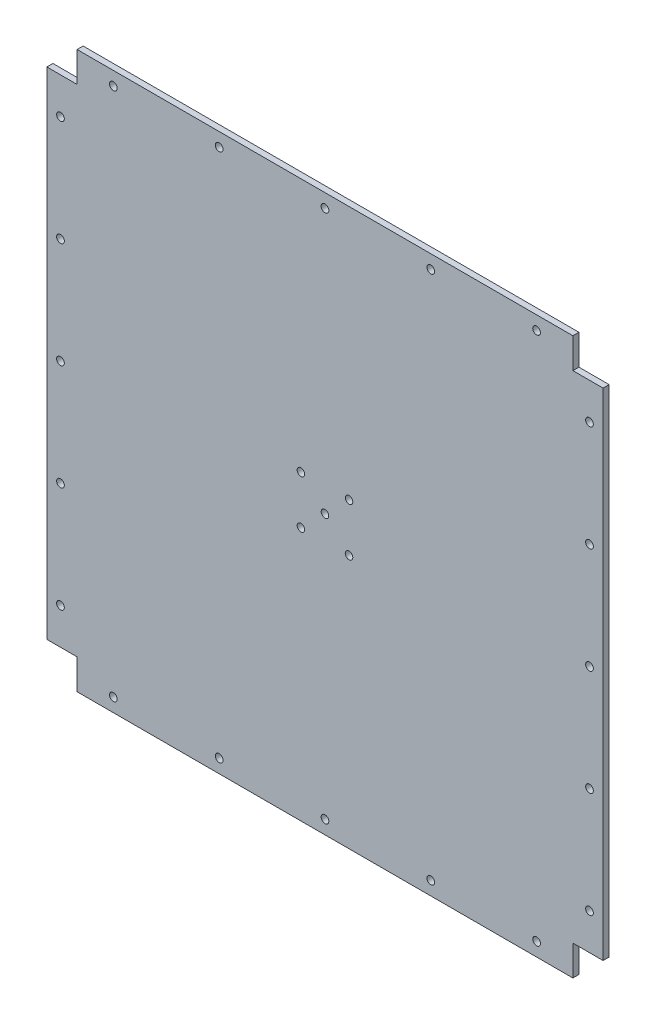
SolidWorks part; units mm, degrees
ref_plane "前视基准面" through (0, 0, 0) normal (0, 0, 1) x (1, 0, 0)
ref_plane "上视基准面" through (0, 0, 0) normal (0, 1, 0) x (1, 0, 0)
ref_plane "右视基准面" through (0, 0, 0) normal (1, 0, 0) x (0, 0, -1)
sketch "草图1" plane through (0, 0, 0) normal (0, 0, 1) x (1, 0, 0)
  line L1 (184, -184) -> (-184, -184)
  line L2 (184, -184) -> (184, 184)
  line L3 (184, 184) -> (-184, 184)
  line L4 (-184, -184) -> (-184, 184)
  line L5 (184, -184) -> (-184, 184) construction
  line L6 (184, 184) -> (-184, -184) construction
  point P0 (0, 0)
  dimension "D1" = 368
  dimension "D2" = 368
extrude "凸台-拉伸1" add sketch "草图1" along normal blind 4
sketch "草图3" plane through (0, 0, 4) normal (0, 0, 1) x (1, 0, 0)
  line L0 (0, -184) -> (0, -175) construction
  line L1 (-184, -184) -> (184, -184) construction
  circle A0 centre (0, -175) radius 2.55
  circle A1 centre (70, -175) radius 2.55
  circle A2 centre (140, -175) radius 2.55
  circle A3 centre (-70, -175) radius 2.55
  circle A4 centre (-140, -175) radius 2.55
  circle A30 centre (-175, 140) radius 2.55
  circle A31 centre (-175, 70) radius 2.55
  circle A32 centre (-175, -70) radius 2.55
  circle A33 centre (-175, -140) radius 2.55
  circle A34 centre (-175, 0) radius 2.55
  circle A35 centre (140, 175) radius 2.55
  circle A36 centre (70, 175) radius 2.55
  circle A37 centre (-70, 175) radius 2.55
  circle A38 centre (-140, 175) radius 2.55
  circle A39 centre (0, 175) radius 2.55
  circle A40 centre (175, -140) radius 2.55
  circle A41 centre (175, -70) radius 2.55
  circle A42 centre (175, 70) radius 2.55
  circle A43 centre (175, 140) radius 2.55
  circle A44 centre (175, 0) radius 2.55
  point P47 (10, -10)
  point P78 (0, 0)
  dimension "D1" = 5.1
  dimension "D2" = 9
  dimension "D3" = 3
  dimension "D4" = 3
  dimension "D6" = 4
extrude "切除-拉伸2" cut sketch "草图3" against normal through all
sketch "草图4" plane through (0, 0, 4) normal (0, 0, 1) x (1, 0, 0)
  line L0 (-164, 184) -> (-164, 164)
  line L1 (-184, -184) -> (-164, -184)
  line L2 (-184, -184) -> (-184, -164)
  line L3 (-184, -164) -> (-164, -164)
  line L4 (-164, -184) -> (-164, -164)
  line L5 (-184, 164) -> (-164, 164)
  line L6 (-184, 184) -> (-164, 184)
  line L7 (-184, 184) -> (-184, 164)
  line L8 (184, 164) -> (164, 164)
  line L9 (164, 184) -> (164, 164)
  line L10 (184, 184) -> (184, 164)
  line L11 (184, 184) -> (164, 184)
  line L12 (164, -184) -> (164, -164)
  line L13 (184, -164) -> (164, -164)
  line L14 (184, -184) -> (164, -184)
  line L15 (184, -184) -> (184, -164)
  point P20 (0, 0)
  dimension "D1" = 20
  dimension "D2" = 20
  dimension "D3" = 4
extrude "切除-拉伸3" cut sketch "草图4" against normal through all contours L0 L5 L7 L6 | L8 L9 L11 L10 | L12 L13 L15 L14 | L2 L1 L4 L3
sketch "草图5" plane through (0, 0, 4) normal (0, 0, 1) x (1, 0, 0)
  line L0 (-184, 0) -> (184, 0) construction
  line L1 (-184, 164) -> (-184, -164) construction
  line L3 (0, 184) -> (0, -184) construction
  line L4 (164, 184) -> (-164, 184) construction
  line L5 (-164, -184) -> (164, -184) construction
  line L6 (-10, 0) -> (-22.5, 0) construction
  line L11 (10, -10) -> (-10, 10) construction
  line L12 (10, 10) -> (-10, -10) construction
  line L13 (0, -10) -> (0, -22.5) construction
  line L14 (10, 0) -> (22.5, 0) construction
  line L15 (0, 10) -> (0, 22.5) construction
  line L16 (-173.9781, 173.9781) -> (0, 0) construction
  line L17 (-184, 0) -> (0, 184) construction
  line L18 (0, 0) -> (-15.9099, 15.9099) construction
  line L19 (-14.489, 14.489) -> (-159.489, 14.489) construction
  line L20 (-14.489, 14.489) -> (-14.489, 159.489) construction
  line L21 (-14.489, 159.489) -> (-159.489, 159.489) construction
  line L22 (-159.489, 14.489) -> (-159.489, 159.489) construction
  line L23 (-14.489, 14.489) -> (-159.489, 159.489) construction
  line L24 (-14.489, 159.489) -> (-159.489, 14.489) construction
  line L25 (0, 0) -> (15.9099, 15.9099) construction
  circle A4 centre (0, 0) radius 2.5
  circle A5 centre (-15.9099, 15.9099) radius 2.5
  circle A7 centre (15.9099, 15.9099) radius 2.5
  circle A8 centre (15.9099, -15.9099) radius 2.5
  circle A9 centre (-15.9099, -15.9099) radius 2.5
  point P4 (-86.989, 86.989)
  point P12 (0, 0)
  dimension "D11" = 5
  dimension "D16" = 5
  dimension "D17" = 5
  dimension "D1" = 20
  dimension "D2" = 20
  dimension "D3" = 12.5
  dimension "D4" = 12.5
  dimension "D5" = 12.5
  dimension "D6" = 12.5
  dimension "D12" = 145
  dimension "D13" = 145
  dimension "D14" = 22.5
  dimension "D15" = 22.5
extrude "切除-拉伸6" cut sketch "草图5" against normal blind 10
sketch "草图6" plane through (0, 0, 0) normal (0, 0, -1) x (-1, 0, 0)
  circle A0 centre (121.8, -122) radius 2
  circle A1 centre (71.8, -72) radius 2
